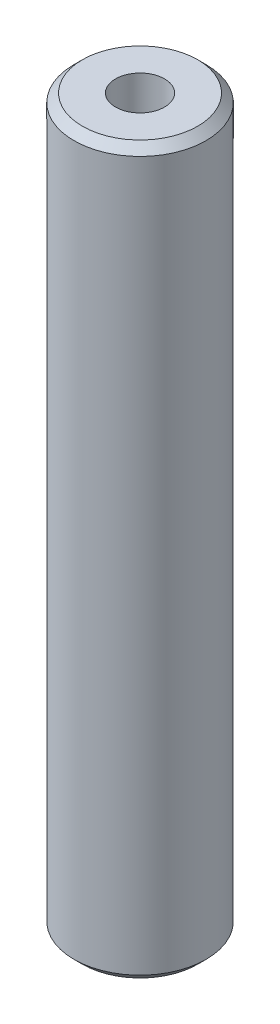
SolidWorks part; units mm, degrees
ref_plane "Front Plane" through (0, 0, 0) normal (0, 0, 1) x (1, 0, 0)
ref_plane "Top Plane" through (0, 0, 0) normal (0, 1, 0) x (1, 0, 0)
ref_plane "Right Plane" through (0, 0, 0) normal (1, 0, 0) x (0, 0, -1)
sketch "Sketch1" plane through (0, 0, 0) normal (0, 1, 0) x (1, 0, 0)
  circle A0 centre (0, 0) radius 45
  dimension "SHAFT_OD" = 90
extrude "Boss-Extrude1" add sketch "Sketch1" along normal blind 494.9802
sketch "Sketch2" plane through (0, 0, 0) normal (0, 1, 0) x (1, 0, 0)
  circle A0 centre (0, 0) radius 16.7016
  dimension "BORE_D" = 33.4032
extrude "Cut-Extrude1" cut sketch "Sketch2" along normal through all
chamfer "Chamfer1" distance 5.6892 angle 45 2 edges at (0, 494.9802, 45) (0, 0, 45)
